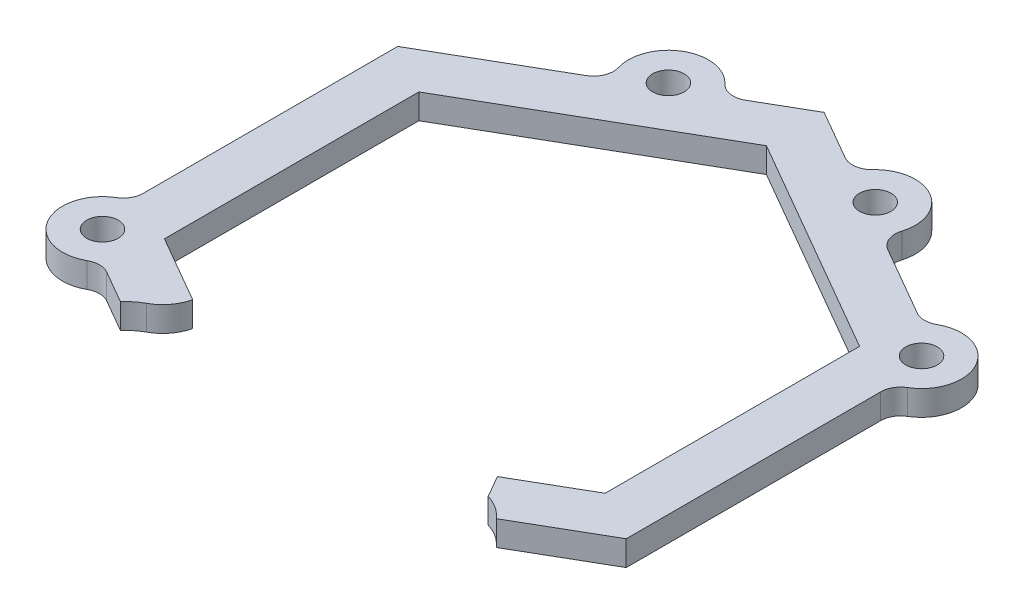
SolidWorks part; units mm, degrees
other "Markup1"
sketch "Sketch19" plane through (45.72, 20.955, -50.8) normal (0.2929, 0.2388, -0.9259) x (0.9546, -0.0187, 0.2972)
ref_plane "Front Plane" through (0, 0, 0) normal (0, 0, 1) x (1, 0, 0)
ref_plane "Top Plane" through (0, 0, 0) normal (0, 1, 0) x (1, 0, 0)
ref_plane "Right Plane" through (0, 0, 0) normal (1, 0, 0) x (0, 0, -1)
sketch "Sketch1" plane through (0, 0, 0) normal (0, 1, 0) x (1, 0, 0)
  line L0 (-13.1445, 33.02) -> (13.1445, 33.02) construction
  line L1 (0, 0) -> (0, 33.02) construction
  line L2 (13.1445, 33.02) -> (13.1445, 39.116) construction
  line L3 (13.1445, 39.116) -> (26.4795, 39.116) construction
  line L4 (0, 33.02) -> (0, 50.8) construction
  circle A0 centre (0, 0) radius 50.8
  circle A2 centre (-13.1445, 33.02) radius 1.905
  circle A3 centre (13.1445, 33.02) radius 1.905
  circle A4 centre (0, 0) radius 48.8
  dimension "D1" = 101.6
  dimension "D2" = 3.81
  dimension "D7" = 6.096
  dimension "D8" = 13.335
  dimension "D3" = 17.78
  dimension "D5" = 3.81
  dimension "D4" = 26.289
  dimension "D6" = 2
extrude "Boss-Extrude1" add sketch "Sketch1" along normal blind 3.175 contours A4 A2 A3 | A0 A4
sketch "Sketch3" plane through (0, 3.175, 0) normal (0, 1, 0) x (1, 0, 0)
  circle A0 centre (0, 0) radius 48.8
  circle A1 centre (0, 0) radius 50.8
  circle A2 centre (0, 0) radius 50.8
  dimension "D1" = 0
  dimension "D2" = 2
extrude "Boss-Extrude3" add sketch "Sketch3" along normal blind 17.78
sketch "Sketch4" plane through (0, 3.175, 0) normal (0, 1, 0) x (1, 0, 0)
  line L0 (0, 0) -> (25.4, 0) construction
  line L1 (25.4, 0) -> (25.4, -41.6687)
  line L2 (0, 0) -> (-25.4, 0) construction
  line L3 (-25.4, 0) -> (-25.4, -41.6687)
  line L4 (0, 0) -> (0, -45.72) construction
  arc A0 (-25.4, -38.0152) -> (25.4, -38.0152) centre (0, 0) ccw
  circle A2 centre (0, 0) radius 48.8 construction
  circle A3 centre (0, 0) radius 48.8 construction
  spline S0 degree 2 poles (-25.4, -20.8343) (0, -32.2542) (25.4, -20.8343) knots 0 0 0 1 1 1
  dimension "D1" = 45.72
  dimension "D3" = 25.4
  dimension "D4" = 25.4
extrude "Cut-Extrude1" cut sketch "Sketch4" against normal through all
fillet "Fillet2" radius 6.35 4 edges at (25.4, 1.5875, 20.8343) (-25.4, 1.5875, 20.8343) (-25.4, 1.5875, 38.0152) (25.4, 1.5875, 38.0152)
sketch "Sketch5" plane through (0, 3.175, 0) normal (0, 1, 0) x (1, 0, 0)
  line L0 (-13.1445, 37.925) -> (13.1445, 37.925)
  line L1 (-18.0495, 33.02) -> (-18.0495, -23.7298)
  line L2 (18.0495, 33.02) -> (18.0495, -23.7298)
  line L3 (-13.1445, 28.115) -> (13.1445, 28.115)
  line L4 (-8.2395, 33.02) -> (-8.2395, -25.9434)
  line L5 (8.2395, 33.02) -> (8.2395, -25.9434)
  line L6 (-8.2395, 3.5383) -> (8.2395, 3.5383)
  line L7 (-8.2395, -2.4617) -> (8.2395, -2.4617)
  circle A0 centre (13.1445, 33.02) radius 1.905 construction
  circle A1 centre (-13.1445, 33.02) radius 1.905 construction
  circle A2 centre (13.1445, 33.02) radius 1.905
  circle A3 centre (-13.1445, 33.02) radius 1.905
  circle A4 centre (-13.1445, 33.02) radius 4.905
  circle A5 centre (13.1445, 33.02) radius 4.905
  arc A6 (-17.2005, -23.9258) -> (-25.4, -30.0005) centre (-19.05, -30.0005) ccw construction
  arc A7 (25.4, -30.0005) -> (17.2005, -23.9258) centre (19.05, -30.0005) ccw construction
  parabola Q0 (-17.2005, -23.9258) -> (17.2005, -23.9258) focus (0, 1.7029) apex (0, -26.5443) construction
  parabola Q1 (-17.2005, -23.9258) -> (17.2005, -23.9258) focus (0, 1.7029) apex (0, -26.5443) construction
  circle M5 centre (13.1445, 33.02) radius 1.905
  circle M6 centre (-13.1445, 33.02) radius 1.905
  arc M9 (-25.4, -30.0005) -> (-17.2005, -23.9258) centre (-19.05, -30.0005) cw
  spline M10 degree 2 poles (-25.4, -20.8343) (0, -32.2542) (25.4, -20.8343) knots 0 0 0 1 1 1 only from (-17.2005, -23.9258) to (17.2005, -23.9258)
  arc M11 (17.2005, -23.9258) -> (25.4, -30.0005) centre (19.05, -30.0005) cw
  dimension "D2" = 6
  dimension "D1" = 3
extrude "Boss-Extrude4" add sketch "Sketch5" along normal blind 1 contours A5 L3 L5 L2 M10 M11 | L4 L7 L5 L6 | A4 L1 L4 L3 M9 M10 | A5 M5 | A5 L5 L3 | A5 L0 A4 L4 L3 L5 | A4 L3 L4 | A4 M6
sketch "Sketch6" plane through (0, 20.955, 0) normal (0, 1, 0) x (1, 0, 0)
  line L0 (0, 0) -> (43.9941, 25.4)
  line L1 (0, 0) -> (43.9941, -25.4)
  line L2 (0, 0) -> (50.8, 0) construction
  circle A0 centre (0, 0) radius 50.8 construction
  circle A1 centre (0, 0) radius 45.72
  circle A2 centre (0, 0) radius 50.8
  circle M4 centre (0, 0) radius 50.8
  circle M5 centre (0, 0) radius 48.8
  dimension "D1" = 101.6
  dimension "D2" = 91.44
  dimension "D3" = 30
  dimension "D4" = 30
extrude "Cut-Extrude2" cut sketch "Sketch6" against normal through all contours A1 L2 L0 M5 | L2 A1 L1 M5 | L2 L1 M5 M4 | L2 A2 L0 M5
sketch "Sketch7" plane through (0, 3.175, 0) normal (0, 1, 0) x (1, 0, 0)
  line L0 (39.5947, -22.86) -> (42.262, -24.4) construction
  line L1 (39.5947, 22.86) -> (42.262, 24.4) construction
  line L2 (39.5947, -22.86) -> (42.262, -24.4)
  line L3 (39.5947, 22.86) -> (42.262, 24.4)
  line L4 (36.823, -23.5692) -> (41.262, -26.1321)
  line L5 (36.823, 23.5692) -> (41.262, 26.1321)
  line L8 (42.262, -24.4) -> (39.5947, -22.86)
  line L9 (39.5947, 22.86) -> (42.262, 24.4)
  line L10 (42.262, -24.4) -> (39.5947, -22.86)
  line L11 (39.5947, 22.86) -> (42.262, 24.4)
  arc A0 (39.5947, -22.86) -> (39.5947, 22.86) centre (0, 0) ccw construction
  arc A1 (39.5947, -22.86) -> (39.5947, 22.86) centre (0, 0) ccw
  arc A2 (36.823, -23.5692) -> (36.823, 23.5692) centre (0, 0) ccw
  arc A5 (39.5947, -22.86) -> (39.5947, 22.86) centre (0, 0) ccw
  arc A6 (42.262, 24.4) -> (42.262, -24.4) centre (0, 0) ccw
  arc A7 (39.5947, -22.86) -> (39.5947, 22.86) centre (0, 0) ccw
  arc A8 (42.262, 24.4) -> (42.262, -24.4) centre (0, 0) ccw
  line M7 (42.262, -24.4) -> (39.5947, -22.86)
  arc M8 (39.5947, -22.86) -> (39.5947, 22.86) centre (0, 0) ccw
  line M9 (39.5947, 22.86) -> (42.262, 24.4)
  arc M10 (42.262, 24.4) -> (42.262, -24.4) centre (0, 0) ccw
  dimension "D1" = 2
  dimension "D2" = 0
extrude "Boss-Extrude5" add sketch "Sketch7" along normal up to surface (17.78 mm away) contours A2 L4 L5 M10 M7 M8 M9 up to face at (-3.336, 20.955, 0)
sketch "Sketch10" plane through (0, 3.175, 0) normal (0, 1, 0) x (1, 0, 0)
  line L0 (-32.9956, -19.05) -> (32.9956, 19.05) construction
  line L1 (0, 37.925) -> (0, 0) construction
  line L2 (-13.1445, 37.925) -> (13.1445, 37.925) construction
  circle A0 centre (-32.9956, -19.05) radius 1.5
  circle A1 centre (32.9956, 19.05) radius 1.5
  dimension "D1" = 3
  dimension "D2" = 3
  dimension "D3" = 76.2
  dimension "D4" = 60
extrude "Cut-Extrude4" cut sketch "Sketch10" against normal through all
sketch "Sketch11" plane through (0, 3.175, 0) normal (0, 1, 0) x (1, 0, 0)
  line L0 (32.9956, 23.09) -> (37.1253, 23.09)
  line L1 (32.9956, 15.01) -> (43.1859, 15.01)
  circle A0 centre (32.9956, 19.05) radius 1.5 construction
  circle A1 centre (-32.9956, -19.05) radius 1.5 construction
  circle A2 centre (32.9956, 19.05) radius 1.5
  circle A3 centre (-32.9956, -19.05) radius 1.5
  circle A4 centre (-32.9956, -19.05) radius 4.04
  circle A5 centre (32.9956, 19.05) radius 4.04
  arc A6 (36.823, -23.5692) -> (36.823, 23.5692) centre (0, 0) ccw construction
  arc A7 (39.5947, -22.86) -> (39.5947, 22.86) centre (0, 0) ccw construction
  arc A8 (36.823, -23.5692) -> (36.823, 23.5692) centre (0, 0) ccw construction
  arc A9 (36.823, -23.5692) -> (36.823, 23.5692) centre (0, 0) ccw
  circle M1 centre (-32.9956, -19.05) radius 1.5
  circle M2 centre (32.9956, 19.05) radius 1.5
  arc M18 (36.823, -23.5692) -> (36.823, 23.5692) centre (0, 0) ccw
  dimension "D1" = 2.54
extrude "Boss-Extrude7" add sketch "Sketch11" along normal up to surface (17.78 mm away) contours A5 L1 L0 M18 | A5 M2 | A4 M1
sketch "Sketch12" plane through (0, 0, 0) normal (0, -1, 0) x (1, 0, 0)
  line L0 (0, 0) -> (35.921, 35.921) construction
  line L1 (0, 0) -> (35.921, -35.921) construction
  line L2 (0, 0) -> (0, 26.5443) construction
  line L3 (0, 0) -> (-35.921, -35.921) construction
  line L4 (0, 0) -> (-35.921, 35.921) construction
  line L7 (39.5947, 22.86) -> (43.9941, 25.4)
  line L8 (43.9941, -25.4) -> (39.5947, -22.86)
  line L9 (39.5947, 22.86) -> (43.9941, 25.4)
  line L10 (43.9941, -25.4) -> (39.5947, -22.86)
  arc A0 (43.9941, 25.4) -> (43.9941, -25.4) centre (0, 0) ccw construction
  circle A1 centre (35.921, 35.921) radius 9.525
  circle A2 centre (35.921, -35.921) radius 9.525
  circle A3 centre (-35.921, -35.921) radius 9.525
  circle A4 centre (-35.921, 35.921) radius 9.525
  arc A7 (39.5947, -22.86) -> (39.5947, 22.86) centre (0, 0) ccw
  arc A8 (43.9941, 25.4) -> (43.9941, -25.4) centre (0, 0) ccw
  arc A9 (39.5947, -22.86) -> (39.5947, 22.86) centre (0, 0) ccw
  arc A10 (43.9941, 25.4) -> (43.9941, -25.4) centre (0, 0) ccw
  parabola Q0 (-17.2005, 23.9258) -> (17.2005, 23.9258) focus (0, -1.7029) apex (0, 26.5443) construction
  parabola Q1 (-8.2395, 25.9434) -> (8.2395, 25.9434) focus (0, -1.7029) apex (0, 26.5443) construction
  arc M14 (43.9941, 25.4) -> (43.9941, -25.4) centre (0, 0) ccw
  dimension "D5" = 19.05
  dimension "D6" = 19.05
  dimension "D7" = 19.05
  dimension "D8" = 19.05
  dimension "D1" = 45
  dimension "D2" = 90
  dimension "D3" = 90
  dimension "D4" = 90
  dimension "D9" = 0
extrude "Boss-Extrude8" add sketch "Sketch12" along normal blind 31.75 contours A1 M14 | A2 M14 | A4 M14 | A3 M14
fillet "Fillet4" radius 3.175 8 edges at (-41.9951, -15.875, -28.5841) (-28.5841, -15.875, -41.9951) (28.5841, -15.875, -41.9951) (41.9951, -15.875, -28.5841) (-28.5841, -15.875, 41.9951) (-41.9951, -15.875, 28.5841) (41.9951, -15.875, 28.5841) (28.5841, -15.875, 41.9951)
sketch "Sketch13" plane through (0, -31.75, 0) normal (0, -1, 0) x (1, 0, 0)
  line L0 (35.921, 35.921) -> (0, 0) construction
  line L1 (35.023, 35.023) -> (30.5329, 39.5131)
  line L2 (35.023, 35.023) -> (39.5131, 30.5329)
  line L3 (39.5131, 30.5329) -> (35.921, 26.9408)
  line L4 (35.921, 26.9408) -> (26.9408, 35.921)
  line L5 (26.9408, 35.921) -> (30.5329, 39.5131)
  line L6 (26.9408, -35.921) -> (35.921, -26.9408)
  line L7 (35.921, -26.9408) -> (39.5131, -30.5329)
  line L8 (35.023, -35.023) -> (39.5131, -30.5329)
  line L9 (35.023, -35.023) -> (30.5329, -39.5131)
  line L10 (30.5329, -39.5131) -> (26.9408, -35.921)
  line L11 (-35.921, -26.9408) -> (-26.9408, -35.921)
  line L12 (-26.9408, -35.921) -> (-30.5329, -39.5131)
  line L13 (-35.023, -35.023) -> (-30.5329, -39.5131)
  line L14 (-35.023, -35.023) -> (-39.5131, -30.5329)
  line L15 (-39.5131, -30.5329) -> (-35.921, -26.9408)
  line L16 (-26.9408, 35.921) -> (-35.921, 26.9408)
  line L17 (-35.921, 26.9408) -> (-39.5131, 30.5329)
  line L18 (-35.023, 35.023) -> (-39.5131, 30.5329)
  line L19 (-35.023, 35.023) -> (-30.5329, 39.5131)
  line L20 (-30.5329, 39.5131) -> (-26.9408, 35.921)
  line L21 (0, 0) -> (0, 26.5443) construction
  line L22 (0, 0) -> (-35.023, 35.023) construction
  line L23 (0, 0) -> (-35.023, -35.023) construction
  line L24 (0, 0) -> (35.023, -35.023) construction
  line L25 (30.5329, 39.5131) -> (31.0981, 40.0784) construction
  line L26 (39.5131, -30.5329) -> (40.0784, -31.0981) construction
  arc A0 (39.7063, 31.6867) -> (31.6867, 39.7063) centre (0, 0) ccw construction
  arc A2 (31.6867, 39.7063) -> (26.5989, 37.8765) centre (29.7063, 37.2247) ccw construction
  arc A3 (39.7063, -31.6867) -> (37.8765, -26.5989) centre (37.2247, -29.7063) ccw construction
  parabola Q0 (-17.2005, 23.9258) -> (17.2005, 23.9258) focus (0, -1.7029) apex (0, 26.5443) construction
  point P32 (0, 0)
  dimension "D1" = 12.7
  dimension "D2" = 6.35
  dimension "D3" = 5.08
  dimension "D5" = 44.45
  dimension "D4" = 4
extrude "Boss-Extrude9" add sketch "Sketch13" along normal blind 15.24
sketch "Sketch15" plane through (-35.023, 0, 35.023) normal (-0.7071, 0, 0.7071) x (0.7071, 0, 0.7071)
  line L0 (6.35, -46.99) -> (-6.35, -31.75) construction
  line L5 (6.35, -31.75) -> (-6.35, -31.75)
  line L6 (-6.35, -31.75) -> (-6.35, -46.99)
  line L7 (-6.35, -46.99) -> (6.35, -46.99)
  line L8 (6.35, -46.99) -> (6.35, -31.75)
  line L9 (6.35, -31.75) -> (-6.35, -31.75)
  line L10 (-6.35, -31.75) -> (-6.35, -46.99)
  line L11 (-6.35, -46.99) -> (6.35, -46.99)
  line L12 (6.35, -46.99) -> (6.35, -31.75)
  circle A0 centre (0, -39.37) radius 2
  dimension "D2" = 4
  dimension "D1" = 0
extrude "Cut-Extrude5" cut sketch "Sketch15" against normal up to next contours A0 L0 | L0 A0
pattern_circular "CirPattern1" count 4 over 360 about axis through (0, 3.175, 0) along (0, -1, 0) of "Cut-Extrude5"
sketch "Sketch17" plane through (0, 0, 0) normal (0, -1, 0) x (1, 0, 0)
  line L0 (0, 39.6662) -> (-34.3519, 19.8331)
  line L1 (0, 36) -> (-31.1769, 18)
  line L2 (-31.1769, 18) -> (-31.1769, -18)
  line L3 (-31.1769, -18) -> (0, -36)
  line L4 (0, -36) -> (31.1769, -18)
  line L5 (31.1769, -18) -> (31.1769, 18)
  line L6 (31.1769, 18) -> (0, 36)
  line L7 (-34.3519, 19.8331) -> (-34.3519, -19.8331)
  line L8 (-34.3519, -19.8331) -> (0, -39.6662)
  line L9 (0, -39.6662) -> (34.3519, -19.8331)
  line L10 (34.3519, -19.8331) -> (34.3519, 19.8331)
  line L11 (34.3519, 19.8331) -> (0, 39.6662)
  line L12 (-34.3519, 0) -> (8.4471, 0) construction
  line L13 (-2.3857, 22.3199) -> (2.1188, 29.765)
  line L16 (43.9941, -25.4) -> (39.5947, -22.86)
  line L17 (39.5947, 22.86) -> (43.9941, 25.4)
  line L18 (43.9941, -25.4) -> (39.5947, -22.86)
  line L19 (39.5947, 22.86) -> (43.9941, 25.4)
  circle A0 centre (0, 0) radius 31.1769 construction
  circle A1 centre (8.4471, 0) radius 8.89
  arc A20 (-26.5989, -37.8765) -> (-37.8765, -26.5989) centre (-35.921, -35.921) ccw
  arc A21 (-31.6867, -39.7063) -> (-26.5989, -37.8765) centre (-29.7063, -37.2247) ccw
  arc A22 (-31.6867, -39.7063) -> (31.6867, -39.7063) centre (0, 0) ccw
  arc A23 (26.5989, -37.8765) -> (31.6867, -39.7063) centre (29.7063, -37.2247) ccw
  arc A24 (37.8765, -26.5989) -> (26.5989, -37.8765) centre (35.921, -35.921) ccw
  arc A25 (39.7063, -31.6867) -> (37.8765, -26.5989) centre (37.2247, -29.7063) ccw
  arc A26 (39.7063, -31.6867) -> (43.9941, -25.4) centre (0, 0) ccw
  arc A27 (39.5947, -22.86) -> (39.5947, 22.86) centre (0, 0) ccw
  arc A28 (43.9941, 25.4) -> (39.7063, 31.6867) centre (0, 0) ccw
  arc A29 (37.8765, 26.5989) -> (39.7063, 31.6867) centre (37.2247, 29.7063) ccw
  arc A30 (26.5989, 37.8765) -> (37.8765, 26.5989) centre (35.921, 35.921) ccw
  arc A31 (31.6867, 39.7063) -> (26.5989, 37.8765) centre (29.7063, 37.2247) ccw
  arc A32 (31.6867, 39.7063) -> (-31.6867, 39.7063) centre (0, 0) ccw
  arc A33 (-26.5989, 37.8765) -> (-31.6867, 39.7063) centre (-29.7063, 37.2247) ccw
  arc A34 (-37.8765, 26.5989) -> (-26.5989, 37.8765) centre (-35.921, 35.921) ccw
  arc A35 (-39.7063, 31.6867) -> (-37.8765, 26.5989) centre (-37.2247, 29.7063) ccw
  arc A36 (-39.7063, 31.6867) -> (-39.7063, -31.6867) centre (0, 0) ccw
  arc A37 (-37.8765, -26.5989) -> (-39.7063, -31.6867) centre (-37.2247, -29.7063) ccw
  arc A38 (-26.5989, -37.8765) -> (-37.8765, -26.5989) centre (-35.921, -35.921) ccw
  arc A39 (-31.6867, -39.7063) -> (-26.5989, -37.8765) centre (-29.7063, -37.2247) ccw
  arc A40 (-31.6867, -39.7063) -> (31.6867, -39.7063) centre (0, 0) ccw
  arc A41 (26.5989, -37.8765) -> (31.6867, -39.7063) centre (29.7063, -37.2247) ccw
  arc A42 (37.8765, -26.5989) -> (26.5989, -37.8765) centre (35.921, -35.921) ccw
  arc A43 (39.7063, -31.6867) -> (37.8765, -26.5989) centre (37.2247, -29.7063) ccw
  arc A44 (39.7063, -31.6867) -> (43.9941, -25.4) centre (0, 0) ccw
  arc A45 (39.5947, -22.86) -> (39.5947, 22.86) centre (0, 0) ccw
  arc A46 (43.9941, 25.4) -> (39.7063, 31.6867) centre (0, 0) ccw
  arc A47 (37.8765, 26.5989) -> (39.7063, 31.6867) centre (37.2247, 29.7063) ccw
  arc A48 (26.5989, 37.8765) -> (37.8765, 26.5989) centre (35.921, 35.921) ccw
  arc A49 (31.6867, 39.7063) -> (26.5989, 37.8765) centre (29.7063, 37.2247) ccw
  arc A50 (31.6867, 39.7063) -> (-31.6867, 39.7063) centre (0, 0) ccw
  arc A51 (-26.5989, 37.8765) -> (-31.6867, 39.7063) centre (-29.7063, 37.2247) ccw
  arc A52 (-37.8765, 26.5989) -> (-26.5989, 37.8765) centre (-35.921, 35.921) ccw
  arc A53 (-39.7063, 31.6867) -> (-37.8765, 26.5989) centre (-37.2247, 29.7063) ccw
  arc A54 (-39.7063, 31.6867) -> (-39.7063, -31.6867) centre (0, 0) ccw
  arc A55 (-37.8765, -26.5989) -> (-39.7063, -31.6867) centre (-37.2247, -29.7063) ccw
  parabola Q1 (-17.2005, 23.9258) -> (17.2005, 23.9258) focus (0, -1.7029) apex (0, 26.5443) construction
  spline S0 degree 2 poles (8.4471, 0) (-30.1546, -5.2232) (-7.5301, 26.0424) knots 0 0 0 1 1 1
  spline S1 degree 1 poles (7.5956, 6.2927) (-2.3857, 22.3199) knots 0 0 1 1 construction
  spline S2 degree 2 poles (7.5956, 6.2927) (4.1843, 5.8332) (-1.3854, 5.5306) (-5.6119, 5.8013) (-7.8686, 6.3471) (-8.9552, 6.8172) (-9.3865, 7.1437) (-9.4373, 7.2217) (-9.4738, 7.2832) (-9.5603, 7.7656) (-9.482, 8.8876) (-8.9355, 11.0689) (-7.229, 14.8558) (-4.3797, 19.5605) (-2.3857, 22.3199) knots 0 0 0 0.09375 0.1875 0.28125 0.34375 0.40625 0.46875 0.53125 0.59375 0.65625 0.71875 0.8125 0.90625 1 1 1
  spline S3 degree 1 poles (9.2985, -6.2927) (-12.6745, 29.765) knots 0 0 1 1 construction
  spline S4 degree 2 poles (9.2985, -6.2927) (5.4721, -6.8126) (-1.2814, -7.1858) (-7.2256, -6.8496) (-11.6507, -5.8206) (-14.9528, -4.4607) (-17.9537, -2.3871) (-20.3784, 0.505) (-21.8607, 3.984) (-22.3364, 7.6121) (-22.0201, 11.1707) (-20.8777, 15.5529) (-18.405, 20.925) (-14.9226, 26.6621) (-12.6745, 29.765) knots 0 0 0 0.09375 0.1875 0.28125 0.34375 0.40625 0.46875 0.53125 0.59375 0.65625 0.71875 0.8125 0.90625 1 1 1
  dimension "D4" = 17.78
  dimension "D1" = 72
  dimension "D3" = 42.799
  dimension "D5" = 6.35
  dimension "D6" = 6.35
  dimension "D7" = 0
  dimension "D2" = 3.175
extrude "Boss-Extrude12" add sketch "Sketch17" along normal blind 16.51 contours A1 S4 A28 A29 L1 L2 L3 L4 L5 L6 A35 L13 S2 | L10 L11 A35 L6 L5 L4 L3 L2 L1 A29 L0 L7 L8 A27 L9 A26
fillet "Fillet8" radius 5.08 3 edges at (-2.3857, -8.255, 22.3199)
sketch "Sketch18" plane through (0, -16.51, 0) normal (0, -1, 0) x (1, 0, 0)
  line L0 (32.7644, 17.0835) -> (0, 36)
  line L1 (0, -39.6662) -> (34.3519, -19.8331)
  line L2 (34.3519, -19.8331) -> (34.3519, 19.8331)
  line L3 (34.3519, 19.8331) -> (0, 39.6662)
  line L4 (0, 39.6662) -> (-34.3519, 19.8331)
  line L5 (-34.3519, 19.8331) -> (-34.3519, -19.8331)
  line L6 (-34.3519, -19.8331) -> (0, -39.6662)
  line L7 (0, 36) -> (-32.7644, 17.0835)
  line L8 (-31.1769, 19.8331) -> (-31.1769, -19.8331)
  line L9 (-1.3646, 24.0075) -> (-2.2796, 22.4952)
  line L10 (-23.8805, 25.8788) -> (-33.119, 20.5449)
  line L11 (-34.3519, 18.4094) -> (-34.3519, -19.8331)
  line L12 (-34.3519, -19.8331) -> (-14.2268, -31.4523)
  line L13 (-11.2457, -33.1735) -> (0, -39.6662)
  line L14 (0, -39.6662) -> (11.2457, -33.1735)
  line L15 (14.2268, -31.4523) -> (33.119, -20.5449)
  line L16 (34.3519, -18.4094) -> (34.3519, 19.8331)
  line L17 (34.3519, 19.8331) -> (23.8805, 25.8788)
  line L18 (-1.3646, 24.0075) -> (-2.2796, 22.4952)
  line L19 (-23.8805, 25.8788) -> (-33.119, 20.5449)
  line L20 (-34.3519, 18.4094) -> (-34.3519, -19.8331)
  line L21 (-34.3519, -19.8331) -> (-14.2268, -31.4523)
  line L22 (-11.2457, -33.1735) -> (0, -39.6662)
  line L23 (0, -39.6662) -> (11.2457, -33.1735)
  line L24 (14.2268, -31.4523) -> (33.119, -20.5449)
  line L25 (34.3519, -18.4094) -> (34.3519, 19.8331)
  line L26 (34.3519, 19.8331) -> (23.8805, 25.8788)
  line L27 (-32.7644, -17.0835) -> (1.5875, -36.9165)
  line L28 (-1.5875, -36.9165) -> (32.7644, -17.0835)
  line L29 (31.1769, -19.8331) -> (31.1769, 19.8331)
  circle A0 centre (0, 0) radius 34.3519 construction
  arc A8 (3.2758, 26.4493) -> (-1.3646, 24.0075) centre (2.9818, 21.3778) ccw
  arc A9 (-2.5028, 22.1575) -> (-2.2796, 22.4952) centre (-6.626, 25.1249) ccw
  arc A10 (2.9039, -6.9502) -> (1.6202, 5.6943) centre (8.4471, 0) ccw
  arc A11 (-19.8143, 17.8575) -> (-22.0517, 24.4048) centre (-24.4531, 19.9282) ccw
  arc A12 (-23.8805, 25.8788) -> (-22.0517, 24.4048) centre (-19.05, 30.0005) ccw
  arc A13 (-11.2457, -33.1735) -> (-14.2268, -31.4523) centre (-13.1445, -33.02) ccw
  arc A14 (14.2268, -31.4523) -> (11.2457, -33.1735) centre (13.1445, -33.02) ccw
  arc A15 (17.2005, 23.9258) -> (23.8805, 25.8788) centre (19.05, 30.0005) ccw
  arc A16 (3.2758, 26.4493) -> (-1.3646, 24.0075) centre (2.9818, 21.3778) ccw
  arc A17 (-2.5028, 22.1575) -> (-2.2796, 22.4952) centre (-6.626, 25.1249) ccw
  arc A18 (2.9039, -6.9502) -> (1.6202, 5.6943) centre (8.4471, 0) ccw
  arc A19 (-19.8143, 17.8575) -> (-22.0517, 24.4048) centre (-24.4531, 19.9282) ccw
  arc A20 (-23.8805, 25.8788) -> (-22.0517, 24.4048) centre (-19.05, 30.0005) ccw
  arc A21 (-11.2457, -33.1735) -> (-14.2268, -31.4523) centre (-13.1445, -33.02) ccw
  arc A22 (14.2268, -31.4523) -> (11.2457, -33.1735) centre (13.1445, -33.02) ccw
  arc A23 (17.2005, 23.9258) -> (23.8805, 25.8788) centre (19.05, 30.0005) ccw
  arc A27 (-34.3519, 18.4094) -> (-33.119, 20.5449) centre (-32.9956, 19.05) ccw
  arc A28 (-34.3519, 18.4094) -> (-33.119, 20.5449) centre (-32.9956, 19.05) ccw
  arc A29 (34.3519, -18.4094) -> (33.119, -20.5449) centre (32.9956, -19.05) ccw
  arc A30 (34.3519, -18.4094) -> (33.119, -20.5449) centre (32.9956, -19.05) ccw
  parabola Q1 (17.2005, 23.9258) -> (3.2758, 26.4493) focus (0, -1.7029) apex (0, 26.5443)
  parabola Q2 (17.2005, 23.9258) -> (3.2758, 26.4493) focus (0, -1.7029) apex (0, 26.5443)
  spline S2 degree 2 poles (2357.9457, 1872.5683) (82.497, 163.0073) (-7.229, 14.8558) (-8.9355, 11.0689) (-9.482, 8.8876) (-9.5603, 7.7656) (-9.4738, 7.2832) (-9.4373, 7.2217) (-9.3865, 7.1437) (-8.9552, 6.8172) (-7.8686, 6.3471) (-5.6119, 5.8013) (-1.3854, 5.5306) (173.8929, 15.0544) (2749.971, 1206.5277) knots -5.629665 -5.629665 -5.629665 0.181038 0.274788 0.368538 0.431038 0.493538 0.556038 0.618538 0.681038 0.743538 0.806038 0.899788 0.993538 6.800424 6.800424 6.800424 only from (-2.5028, 22.1575) to (1.6202, 5.6943)
  spline S3 degree 2 poles (2553.5255, 1567.9708) (232.3364, 5.7259) (-1.2814, -7.1858) (-7.2256, -6.8496) (-11.6507, -5.8206) (-14.9528, -4.4607) (-17.9537, -2.3871) (-20.3784, 0.505) (-21.8607, 3.984) (-22.3364, 7.6121) (-22.0201, 11.1707) (27.5117, 201.1732) (2900.7243, 680.316) knots -6.298557 -6.298557 -6.298557 0.09375 0.1875 0.28125 0.34375 0.40625 0.46875 0.53125 0.59375 0.65625 0.71875 7.430945 7.430945 7.430945 only from (2.9039, -6.9502) to (-19.8143, 17.8575)
  spline S4 degree 2 poles (-2.5028, 22.1575) (-4.4217, 19.4911) (-7.229, 14.8558) (-8.9355, 11.0689) (-9.482, 8.8876) (-9.5603, 7.7656) (-9.4738, 7.2832) (-9.4373, 7.2217) (-9.3865, 7.1437) (-8.9552, 6.8172) (-7.8686, 6.3471) (-5.6119, 5.8013) (-1.3854, 5.5306) (1.5093, 5.6879) (1.6202, 5.6943) knots 0.090051 0.090051 0.090051 0.181038 0.274788 0.368538 0.431038 0.493538 0.556038 0.618538 0.681038 0.743538 0.806038 0.899788 0.993538 0.997237 0.997237 0.997237
  spline S5 degree 2 poles (2.9039, -6.9502) (2.4964, -6.977) (-1.2814, -7.1858) (-7.2256, -6.8496) (-11.6507, -5.8206) (-14.9528, -4.4607) (-17.9537, -2.3871) (-20.3784, 0.505) (-21.8607, 3.984) (-22.3364, 7.6121) (-22.0201, 11.1707) (-20.9264, 15.366) (-19.8143, 17.8575) knots 0.082614 0.082614 0.082614 0.09375 0.1875 0.28125 0.34375 0.40625 0.46875 0.53125 0.59375 0.65625 0.71875 0.805839 0.805839 0.805839
  point P2 (-55.8963, 30.0005)
  dimension "D1" = 0
  dimension "D2" = 3.175
extrude "Boss-Extrude13" add sketch "Sketch18" along normal blind 1.5
fillet "Fillet9" radius 5.08 2 edges at (2.9039, -8.255, -6.9502) (1.6202, -8.255, 5.6943)
sketch "Sketch20" plane through (0, -18.01, 0) normal (0, -1, 0) x (1, 0, 0)
  line L0 (-32.9956, 22.55) -> (-34.3519, 22.55)
  line L1 (-34.3519, 18.4094) -> (-34.3519, -19.8331) construction
  line L2 (-32.9956, 15.55) -> (-34.3519, 15.55)
  line L3 (32.9956, -15.55) -> (34.3519, -15.55)
  line L6 (34.3519, -18.4094) -> (34.3519, 19.8331) construction
  line L7 (34.3519, -18.4094) -> (34.3519, 19.8331) construction
  line L8 (32.9956, -22.55) -> (34.3519, -22.55)
  line L17 (-23.8805, 25.8788) -> (-33.119, 20.5449)
  line L18 (-23.8805, 25.8788) -> (-33.119, 20.5449)
  line L19 (-25.4, 34.4542) -> (-25.4, 30.0005)
  line L20 (-25.4, 34.4542) -> (-25.4, 30.0005)
  line L21 (25.4, 30.0005) -> (25.4, 34.4542)
  line L22 (25.4, 30.0005) -> (25.4, 34.4542)
  line L23 (34.3519, 19.8331) -> (23.8805, 25.8788)
  line L24 (34.3519, 19.8331) -> (23.8805, 25.8788)
  line L25 (34.3519, -18.4094) -> (34.3519, 19.8331)
  line L26 (34.3519, -18.4094) -> (34.3519, 19.8331)
  line L27 (14.2268, -31.4523) -> (33.119, -20.5449)
  line L28 (14.2268, -31.4523) -> (33.119, -20.5449)
  line L29 (0, -39.6662) -> (11.2457, -33.1735)
  line L30 (0, -39.6662) -> (11.2457, -33.1735)
  line L31 (-11.2457, -33.1735) -> (0, -39.6662)
  line L32 (-11.2457, -33.1735) -> (0, -39.6662)
  line L33 (-34.3519, -19.8331) -> (-14.2268, -31.4523)
  line L34 (-34.3519, -19.8331) -> (-14.2268, -31.4523)
  line L35 (-34.3519, 18.4094) -> (-34.3519, -19.8331)
  line L36 (-34.3519, 18.4094) -> (-34.3519, -19.8331)
  line L37 (-23.8805, 25.8788) -> (-33.119, 20.5449)
  line L38 (-23.8805, 25.8788) -> (-33.119, 20.5449)
  line L39 (-25.4, 34.4542) -> (-25.4, 30.0005)
  line L40 (-25.4, 34.4542) -> (-25.4, 30.0005)
  line L41 (25.4, 30.0005) -> (25.4, 34.4542)
  line L42 (25.4, 30.0005) -> (25.4, 34.4542)
  line L43 (34.3519, 19.8331) -> (23.8805, 25.8788)
  line L44 (34.3519, 19.8331) -> (23.8805, 25.8788)
  line L45 (34.3519, -18.4094) -> (34.3519, 19.8331)
  line L46 (34.3519, -18.4094) -> (34.3519, 19.8331)
  line L47 (14.2268, -31.4523) -> (33.119, -20.5449)
  line L48 (14.2268, -31.4523) -> (33.119, -20.5449)
  line L49 (0, -39.6662) -> (11.2457, -33.1735)
  line L50 (0, -39.6662) -> (11.2457, -33.1735)
  line L51 (-11.2457, -33.1735) -> (0, -39.6662)
  line L52 (-11.2457, -33.1735) -> (0, -39.6662)
  line L53 (-34.3519, -19.8331) -> (-14.2268, -31.4523)
  line L54 (-34.3519, -19.8331) -> (-14.2268, -31.4523)
  line L55 (-34.3519, 18.4094) -> (-34.3519, -19.8331)
  line L56 (-34.3519, 18.4094) -> (-34.3519, -19.8331)
  arc A0 (-11.2457, -33.1735) -> (-14.2268, -31.4523) centre (-13.1445, -33.02) ccw construction
  arc A1 (-33.119, 20.5449) -> (-34.3519, 18.4094) centre (-32.9956, 19.05) ccw
  arc A2 (-33.119, 20.5449) -> (-34.3519, 18.4094) centre (-32.9956, 19.05) ccw
  arc A3 (33.119, -20.5449) -> (34.3519, -18.4094) centre (32.9956, -19.05) ccw
  arc A4 (33.119, -20.5449) -> (34.3519, -18.4094) centre (32.9956, -19.05) ccw
  arc A5 (14.2268, -31.4523) -> (11.2457, -33.1735) centre (13.1445, -33.02) ccw construction
  arc A6 (-11.2457, -33.1735) -> (-14.2268, -31.4523) centre (-13.1445, -33.02) ccw
  arc A7 (14.2268, -31.4523) -> (11.2457, -33.1735) centre (13.1445, -33.02) ccw
  arc A8 (11.2457, -33.1735) -> (14.2268, -31.4523) centre (13.1445, -33.02) ccw construction
  arc A9 (-14.2268, -31.4523) -> (-11.2457, -33.1735) centre (-13.1445, -33.02) ccw construction
  arc A10 (11.2457, -33.1735) -> (14.2268, -31.4523) centre (13.1445, -33.02) ccw
  arc A11 (-14.2268, -31.4523) -> (-11.2457, -33.1735) centre (-13.1445, -33.02) ccw
  circle A12 centre (-32.9956, 19.05) radius 3.5
  circle A13 centre (32.9956, -19.05) radius 3.5
  arc A14 (9.2522, -33.3346) -> (15.3631, -29.8065) centre (13.1445, -33.02) ccw
  arc A15 (15.3631, -29.8065) -> (9.2522, -33.3346) centre (13.1445, -33.02) ccw
  arc A16 (-15.3631, -29.8065) -> (-9.2522, -33.3346) centre (-13.1445, -33.02) ccw
  arc A17 (-9.2522, -33.3346) -> (-15.3631, -29.8065) centre (-13.1445, -33.02) ccw
  arc A27 (-25.4, 30.0005) -> (-23.8805, 25.8788) centre (-19.05, 30.0005) ccw
  arc A28 (-25.4, 30.0005) -> (-23.8805, 25.8788) centre (-19.05, 30.0005) ccw
  arc A29 (-22.1226, 40.0114) -> (-25.4, 34.4542) centre (-19.05, 34.4542) ccw
  arc A30 (-22.1226, 40.0114) -> (-25.4, 34.4542) centre (-19.05, 34.4542) ccw
  arc A31 (22.1226, 40.0114) -> (-22.1226, 40.0114) centre (0, 0) ccw
  arc A32 (22.1226, 40.0114) -> (-22.1226, 40.0114) centre (0, 0) ccw
  arc A33 (25.4, 34.4542) -> (22.1226, 40.0114) centre (19.05, 34.4542) ccw
  arc A34 (25.4, 34.4542) -> (22.1226, 40.0114) centre (19.05, 34.4542) ccw
  arc A35 (23.8805, 25.8788) -> (25.4, 30.0005) centre (19.05, 30.0005) ccw
  arc A36 (23.8805, 25.8788) -> (25.4, 30.0005) centre (19.05, 30.0005) ccw
  arc A37 (33.119, -20.5449) -> (34.3519, -18.4094) centre (32.9956, -19.05) ccw
  arc A38 (33.119, -20.5449) -> (34.3519, -18.4094) centre (32.9956, -19.05) ccw
  arc A39 (11.2457, -33.1735) -> (14.2268, -31.4523) centre (13.1445, -33.02) ccw
  arc A40 (11.2457, -33.1735) -> (14.2268, -31.4523) centre (13.1445, -33.02) ccw
  arc A41 (-14.2268, -31.4523) -> (-11.2457, -33.1735) centre (-13.1445, -33.02) ccw
  arc A42 (-14.2268, -31.4523) -> (-11.2457, -33.1735) centre (-13.1445, -33.02) ccw
  arc A43 (-25.4, 30.0005) -> (-23.8805, 25.8788) centre (-19.05, 30.0005) ccw
  arc A44 (-25.4, 30.0005) -> (-23.8805, 25.8788) centre (-19.05, 30.0005) ccw
  arc A45 (-22.1226, 40.0114) -> (-25.4, 34.4542) centre (-19.05, 34.4542) ccw
  arc A46 (-22.1226, 40.0114) -> (-25.4, 34.4542) centre (-19.05, 34.4542) ccw
  arc A47 (22.1226, 40.0114) -> (-22.1226, 40.0114) centre (0, 0) ccw
  arc A48 (22.1226, 40.0114) -> (-22.1226, 40.0114) centre (0, 0) ccw
  arc A49 (25.4, 34.4542) -> (22.1226, 40.0114) centre (19.05, 34.4542) ccw
  arc A50 (25.4, 34.4542) -> (22.1226, 40.0114) centre (19.05, 34.4542) ccw
  arc A51 (23.8805, 25.8788) -> (25.4, 30.0005) centre (19.05, 30.0005) ccw
  arc A52 (23.8805, 25.8788) -> (25.4, 30.0005) centre (19.05, 30.0005) ccw
  arc A53 (11.2457, -33.1735) -> (14.2268, -31.4523) centre (13.1445, -33.02) ccw
  arc A54 (11.2457, -33.1735) -> (14.2268, -31.4523) centre (13.1445, -33.02) ccw
  arc A55 (-14.2268, -31.4523) -> (-11.2457, -33.1735) centre (-13.1445, -33.02) ccw
  arc A56 (-14.2268, -31.4523) -> (-11.2457, -33.1735) centre (-13.1445, -33.02) ccw
  arc A57 (-33.119, 20.5449) -> (-34.3519, 18.4094) centre (-32.9956, 19.05) ccw
  arc A58 (-33.119, 20.5449) -> (-34.3519, 18.4094) centre (-32.9956, 19.05) ccw
  line M13 (-34.3519, 18.4094) -> (-34.3519, -19.8331)
  line M14 (-34.3519, -19.8331) -> (-14.2268, -31.4523)
  line M16 (-11.2457, -33.1735) -> (0, -39.6662)
  line M17 (0, -39.6662) -> (11.2457, -33.1735)
  line M19 (14.2268, -31.4523) -> (33.119, -20.5449)
  line M20 (34.3519, -18.4094) -> (34.3519, 19.8331)
  dimension "D1" = 0
  dimension "D2" = 0
  dimension "D3" = 2
  dimension "D4" = 2
extrude "Boss-Extrude14" add sketch "Sketch20" against normal up to surface (18.01 mm away) contours A12 L2 L0 M13 | A13 L3 L8 M20 | A16 A11 M14 M16 | A14 A10 M17 M19 | A13 A4 L48 M20 | L38 A12 A2 M13
sketch "Sketch21" plane through (0, -18.01, 0) normal (0, -1, 0) x (1, 0, 0)
  line L1 (-21.1509, 23.7885) -> (-31.1769, 18) construction
  line L2 (-21.1509, 23.7885) -> (-31.1769, 18)
  line L3 (31.1769, 18) -> (20.9084, 23.9285) construction
  line L4 (31.1769, -18) -> (31.1769, 18) construction
  line L5 (0, -36) -> (31.1769, -18) construction
  line L6 (-31.1769, -18) -> (0, -36) construction
  line L7 (-31.1769, 18) -> (-31.1769, -18) construction
  line L8 (31.1769, 18) -> (20.9084, 23.9285)
  line L9 (31.1769, -18) -> (31.1769, 18)
  line L10 (0, -36) -> (31.1769, -18)
  line L11 (-31.1769, -18) -> (0, -36)
  line L12 (-31.1769, 18) -> (-31.1769, -18)
  line L13 (-19.5038, 21.0733) -> (-28.0019, 16.1669)
  line L14 (-28.0019, 16.1669) -> (-28.0019, -16.1669)
  line L15 (-28.0019, -16.1669) -> (0, -32.3338)
  line L16 (0, -32.3338) -> (28.0019, -16.1669)
  line L17 (28.0019, -16.1669) -> (28.0019, 16.1669)
  line L18 (28.0019, 16.1669) -> (19.3209, 21.1789)
  line L19 (20.9084, 23.9285) -> (19.3209, 21.1789)
  line L20 (-19.5634, 21.0389) -> (-28.0019, 16.1669) construction
  line L26 (-21.1509, 23.7885) -> (-31.1769, 18)
  line L27 (-31.1769, 18) -> (-31.1769, -18)
  line L28 (-31.1769, -18) -> (0, -36)
  line L29 (0, -36) -> (31.1769, -18)
  line L30 (31.1769, -18) -> (31.1769, 18)
  line L31 (31.1769, 18) -> (20.9084, 23.9285)
  line L32 (-1.3646, 24.0075) -> (-2.2796, 22.4952)
  line L33 (-21.1509, 23.7885) -> (-31.1769, 18)
  line L34 (-31.1769, 18) -> (-31.1769, -18)
  line L35 (-31.1769, -18) -> (0, -36)
  line L36 (0, -36) -> (31.1769, -18)
  line L37 (31.1769, -18) -> (31.1769, 18)
  line L38 (31.1769, 18) -> (20.9084, 23.9285)
  line L39 (-1.3646, 24.0075) -> (-2.2796, 22.4952)
  circle A1 centre (13.1445, -33.02) radius 1.905
  circle A2 centre (13.1445, -33.02) radius 1.905
  circle A3 centre (-13.1445, -33.02) radius 1.905
  circle A4 centre (-13.1445, -33.02) radius 1.905
  arc A15 (4.0204, -7.7095) -> (2.7243, 6.8031) centre (8.4471, 0) ccw
  arc A16 (4.0204, -7.7095) -> (1.2726, -7.0397) centre (1.4909, -12.115) ccw
  arc A17 (-19.8143, 17.8575) -> (-21.1509, 23.7885) centre (-24.4531, 19.9282) ccw
  arc A18 (17.2005, 23.9258) -> (20.9084, 23.9285) centre (19.05, 30.0005) ccw
  arc A19 (3.2758, 26.4493) -> (-1.3646, 24.0075) centre (2.9818, 21.3778) ccw
  arc A20 (-2.5028, 22.1575) -> (-2.2796, 22.4952) centre (-6.626, 25.1249) ccw
  arc A21 (-0.4415, 5.6116) -> (2.7243, 6.8031) centre (-0.5458, 10.6906) ccw
  arc A22 (4.0204, -7.7095) -> (2.7243, 6.8031) centre (8.4471, 0) ccw
  arc A23 (4.0204, -7.7095) -> (1.2726, -7.0397) centre (1.4909, -12.115) ccw
  arc A24 (-19.8143, 17.8575) -> (-21.1509, 23.7885) centre (-24.4531, 19.9282) ccw
  arc A25 (17.2005, 23.9258) -> (20.9084, 23.9285) centre (19.05, 30.0005) ccw
  arc A26 (3.2758, 26.4493) -> (-1.3646, 24.0075) centre (2.9818, 21.3778) ccw
  arc A27 (-2.5028, 22.1575) -> (-2.2796, 22.4952) centre (-6.626, 25.1249) ccw
  arc A28 (-0.4415, 5.6116) -> (2.7243, 6.8031) centre (-0.5458, 10.6906) ccw
  circle A44 centre (-32.9956, 19.05) radius 1.5
  circle A45 centre (-32.9956, 19.05) radius 1.5
  circle A49 centre (32.9956, -19.05) radius 1.5
  circle A50 centre (32.9956, -19.05) radius 1.5
  parabola Q1 (17.2005, 23.9258) -> (3.2758, 26.4493) focus (0, -1.7029) apex (0, 26.5443)
  parabola Q2 (17.2005, 23.9258) -> (3.2758, 26.4493) focus (0, -1.7029) apex (0, 26.5443)
  spline S2 degree 2 poles (2436.0828, 1740.2281) (205.7513, -18.8948) (-7.2256, -6.8496) (-11.6507, -5.8206) (-14.9528, -4.4607) (-17.9537, -2.3871) (-20.3784, 0.505) (-21.8607, 3.984) (-22.3364, 7.6121) (-22.0201, 11.1707) (27.5119, 201.1741) (2900.7519, 680.3206) knots -6.436806 -6.436806 -6.436806 0.1875 0.28125 0.34375 0.40625 0.46875 0.53125 0.59375 0.65625 0.71875 7.430977 7.430977 7.430977 only from (1.2726, -7.0397) to (-19.8143, 17.8575)
  spline S3 degree 2 poles (2357.9452, 1872.5679) (82.4969, 163.0072) (-7.229, 14.8558) (-8.9355, 11.0689) (-9.482, 8.8876) (-9.5603, 7.7656) (-9.4738, 7.2832) (-9.4373, 7.2217) (-9.3865, 7.1437) (-8.9552, 6.8172) (-7.8686, 6.3471) (-5.6119, 5.8013) (126.5924, -2.6676) (2801.7195, 1075.4316) knots -5.593633 -5.593633 -5.593633 0.217069 0.310819 0.404569 0.467069 0.529569 0.592069 0.654569 0.717069 0.779569 0.842069 0.935819 6.70703 6.70703 6.70703 only from (-2.5028, 22.1575) to (-0.4415, 5.6116)
  spline S4 degree 2 poles (1.2726, -7.0397) (-1.6461, -7.1652) (-7.2256, -6.8496) (-11.6507, -5.8206) (-14.9528, -4.4607) (-17.9537, -2.3871) (-20.3784, 0.505) (-21.8607, 3.984) (-22.3364, 7.6121) (-22.0201, 11.1707) (-20.9264, 15.366) (-19.8143, 17.8575) knots 0.105255 0.105255 0.105255 0.1875 0.28125 0.34375 0.40625 0.46875 0.53125 0.59375 0.65625 0.71875 0.805839 0.805839 0.805839
  spline S5 degree 2 poles (-2.5028, 22.1575) (-4.4217, 19.4911) (-7.229, 14.8558) (-8.9355, 11.0689) (-9.482, 8.8876) (-9.5603, 7.7656) (-9.4738, 7.2832) (-9.4373, 7.2217) (-9.3865, 7.1437) (-8.9552, 6.8172) (-7.8686, 6.3471) (-5.6119, 5.8013) (-2.1142, 5.5773) (-0.4415, 5.6116) knots 0.126082 0.126082 0.126082 0.217069 0.310819 0.404569 0.467069 0.529569 0.592069 0.654569 0.717069 0.779569 0.842069 0.935819 0.997237 0.997237 0.997237
  line M16 (16.0433, -30.4036) -> (30.8795, -21.8379)
  line M21 (34.3519, -15.8235) -> (34.3519, 19.8331)
  line M22 (34.3519, 19.8331) -> (23.8805, 25.8788)
  arc M23 (23.8805, 25.8788) -> (20.9084, 23.9285) centre (19.05, 30.0005) cw
  line M24 (20.9084, 23.9285) -> (31.1769, 18)
  line M25 (31.1769, 18) -> (31.1769, -18)
  line M26 (31.1769, -18) -> (0, -36)
  line M27 (0, -36) -> (-31.1769, -18)
  line M28 (-31.1769, -18) -> (-31.1769, 18)
  line M29 (-31.1769, 18) -> (-21.1509, 23.7885)
  arc M30 (-21.1509, 23.7885) -> (-22.0517, 24.4048) centre (-24.4531, 19.9282) ccw
  arc M31 (-22.0517, 24.4048) -> (-23.8805, 25.8788) centre (-19.05, 30.0005) cw
  line M32 (-23.8805, 25.8788) -> (-30.8795, 21.8379)
  line M37 (-34.3519, 15.8235) -> (-34.3519, -19.8331)
  line M38 (-34.3519, -19.8331) -> (-16.0433, -30.4036)
  line M40 (-9.4292, -34.2222) -> (0, -39.6662)
  line M41 (0, -39.6662) -> (9.4292, -34.2222)
  circle M42 centre (13.1445, -33.02) radius 1.905
  circle M43 centre (-13.1445, -33.02) radius 1.905
  circle M100 centre (32.9956, -19.05) radius 1.5
  circle M101 centre (-32.9956, 19.05) radius 1.5
  arc M198 (-30.8795, 21.8379) -> (-34.3519, 15.8235) centre (-32.9956, 19.05) ccw
  arc M199 (-16.0433, -30.4036) -> (-9.4292, -34.2222) centre (-13.1445, -33.02) ccw
  arc M200 (9.4292, -34.2222) -> (16.0433, -30.4036) centre (13.1445, -33.02) ccw
  arc M201 (30.8795, -21.8379) -> (34.3519, -15.8235) centre (32.9956, -19.05) ccw
  dimension "D1" = 0
  dimension "D2" = 0
  dimension "D3" = 0
  dimension "D4" = 0
  dimension "D5" = 3.175
  dimension "D6" = 0
extrude "Boss-Extrude15" add sketch "Sketch21" along normal blind 3.175 contours M32 M198 M37 M38 M199 M40 M41 M200 M16 M201 M21 M22 M23 M24 M25 M26 M27 M28 M29 M30 M31 M100 M42 M43 M101 | L13 A24 L19 L18 L17 L16 L15 L14 M29 M28 M27 M26 M25 M24
sketch "Sketch22" plane through (0, 20.955, 0) normal (0, 1, 0) x (1, 0, 0)
  circle A0 centre (0, 0) radius 73.3024
extrude "Cut-Extrude6" cut sketch "Sketch22" against normal up to surface (38.965 mm away) up to face at (-0.0148, -18.01, 1.5548)
sketch "Sketch24" plane through (0, -21.185, 0) normal (0, -1, 0) x (1, 0, 0)
  circle A0 centre (-32.9956, 19.05) radius 2
  circle A1 centre (-13.1445, -33.02) radius 2
  circle A2 centre (13.1445, -33.02) radius 2
  circle A3 centre (32.9956, -19.05) radius 2
  dimension "D1" = 4
  dimension "D2" = 4
  dimension "D3" = 4
  dimension "D4" = 4
extrude "Cut-Extrude7" cut sketch "Sketch24" against normal up to surface (3.175 mm away) up to face at (-0.0407, -18.01, -3.0504)
sketch "Sketch25" plane through (0, -21.185, 0) normal (0, -1, 0) x (1, 0, 0)
  circle A70 centre (-32.9956, 19.05) radius 5.08
  circle A71 centre (-13.1445, -33.02) radius 5.08
  circle A72 centre (13.1445, -33.02) radius 5.08
  circle A73 centre (32.9956, -19.05) radius 5.08
  circle A74 centre (32.9956, -19.05) radius 2 construction
  circle A75 centre (13.1445, -33.02) radius 2 construction
  circle A76 centre (-13.1445, -33.02) radius 2 construction
  circle A77 centre (-32.9956, 19.05) radius 2 construction
  circle A78 centre (32.9956, -19.05) radius 2
  circle A79 centre (13.1445, -33.02) radius 2
  circle A80 centre (-13.1445, -33.02) radius 2
  circle A81 centre (-32.9956, 19.05) radius 2
  dimension "D1" = 10.16
  dimension "D2" = 10.16
  dimension "D3" = 10.16
  dimension "D4" = 10.16
extrude "Boss-Extrude16" add sketch "Sketch25" against normal up to surface (3.175 mm away)
fillet "Fillet10" radius 2.54 8 edges at (-29.434, -19.5975, 22.6724) (-34.3519, -19.5975, 14.1544) (-8.394, -19.5975, -34.8199) (-17.0785, -19.5975, -29.8059) (34.3519, -19.5975, -14.1544) (29.434, -19.5975, -22.6724) (17.0785, -19.5975, -29.8059) (8.394, -19.5975, -34.8199)
